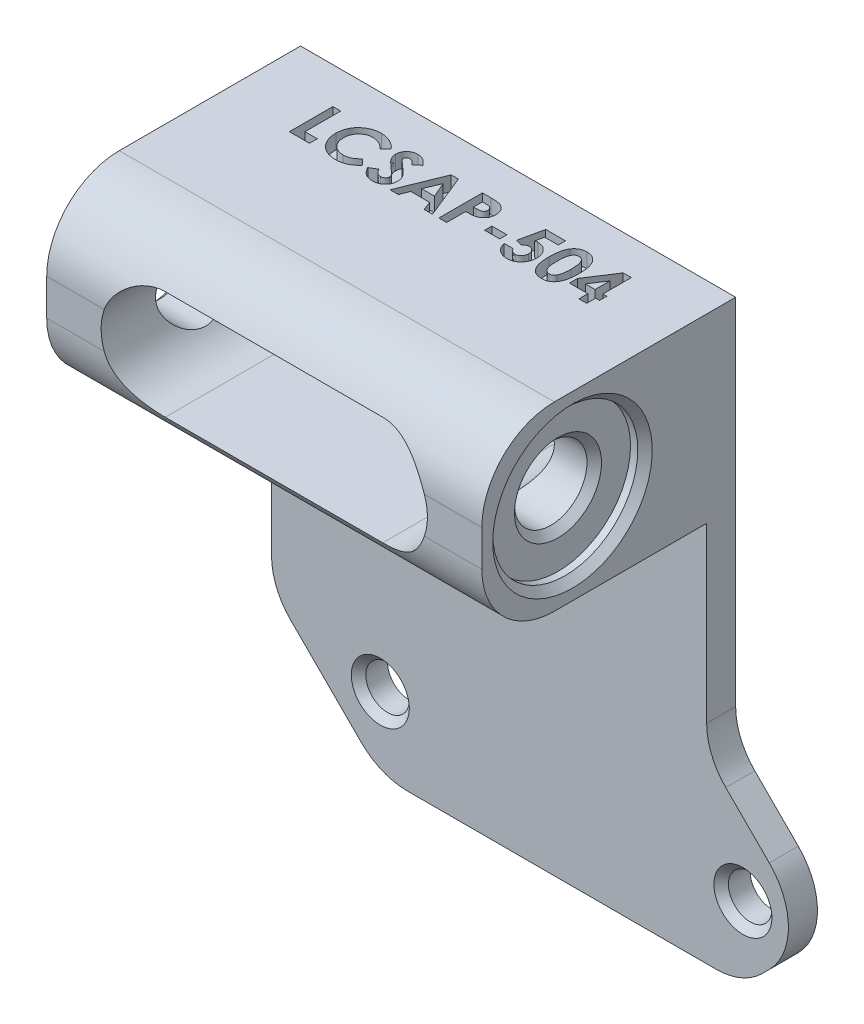
SolidWorks part; units mm, degrees
ref_plane "Front Plane" through (0, 0, 0) normal (0, 0, 1) x (1, 0, 0)
ref_plane "Top Plane" through (0, 0, 0) normal (0, 1, 0) x (1, 0, 0)
ref_plane "Right Plane" through (0, 0, 0) normal (1, 0, 0) x (0, 0, -1)
sketch "Sketch1" plane through (0, 0, 0) normal (0, 0, 1) x (1, 0, 0)
  line L0 (0, 0) -> (50.8, 0)
  line L1 (0, 0) -> (0, -15.875)
  line L3 (9.525, -49.276) -> (41.275, -49.276)
  line L5 (50.8, 0) -> (50.8, -15.875)
  line L7 (9.525, -42.926) -> (25.4, -49.276) construction
  line L8 (25.4, -49.276) -> (41.275, -42.926) construction
  line L9 (0, -15.875) -> (50.8, -15.875)
  line L10 (9.525, -49.276) -> (0, -39.751)
  line L11 (0, -39.751) -> (0, -15.875)
  line L12 (41.275, -49.276) -> (50.8, -39.751)
  line L13 (50.8, -39.751) -> (50.8, -15.875)
  circle A0 centre (9.525, -42.926) radius 1.905
  circle A1 centre (41.275, -42.926) radius 1.905
  dimension "D5" = 3.81
  dimension "D6" = 31.75
  dimension "D7" = 6.35
  dimension "D1" = 15.875
  dimension "D2" = 31.75
  dimension "D3" = 50.8
  dimension "D4" = 49.276
  dimension "D10" = 45
extrude "Boss-Extrude1" add sketch "Sketch1" along normal blind 2.54 contours L1 L9 L5 L0 | L9 L3 A1 A0 region at (25.4, -7.9375, 0) region at (25.4, -31.6514, 0)
extrude "Boss-Extrude2" add sketch "Sketch1<3>" along normal blind 22.225 contours L1 L9 L5 L0 region at (25.4, -7.9375, 0)
sketch "Sketch1<3>" plane through (0, 0, 0) normal (0, 0, 1) x (1, 0, 0) same geometry as "Sketch1"
sketch "Sketch7" plane through (0, 0, 22.225) normal (0, 0, 1) x (1, 0, 0)
  line L1 (50.8, 0) -> (38.1, 0)
  line L2 (50.8, 0) -> (50.8, -33.401)
  line L3 (50.8, -33.401) -> (38.1, -33.401) construction
  line L4 (38.1, 0) -> (38.1, -33.401)
  line L9 (38.1, -33.401) -> (50.8, -46.101)
  line L10 (50.8, -46.101) -> (50.8, -33.401)
  line L11 (44.45, -39.751) -> (41.275, -42.926) construction
  line L12 (41.275, -42.926) -> (44.45, -46.101) construction
  line L14 (41.275, -49.276) -> (50.8, -39.751) construction
  dimension "D1" = 12.7
  dimension "D2" = 45
extrude "Cut-Extrude6" cut sketch "Sketch7" against normal through all
fillet "Fillet2" radius 5.715 5 edges at (0, -39.751, 1.27) (9.525, -49.276, 1.27) (41.275, -49.276, 1.27) (38.1, -33.401, 1.27) (47.625, -42.926, 1.27)
sketch "Sketch2" plane through (38.1, 0, 0) normal (1, 0, 0) x (0, 0, -1)
  line L0 (-22.225, -15.875) -> (-6.35, 0) construction
  line L1 (0, 0) -> (-22.225, 0) construction
  line L2 (-22.225, 0) -> (-22.225, -15.875) construction
  circle A0 centre (-14.2875, -7.9375) radius 3.175
  dimension "D1" = 6.35
  dimension "D2" = 15.875
  dimension "D3" = 15.875
extrude "Cut-Extrude1" cut sketch "Sketch2" against normal through all
sketch "Sketch3" plane through (38.1, 0, 0) normal (1, 0, 0) x (0, 0, -1)
  circle A0 centre (-14.2875, -7.9375) radius 6.35
  dimension "D1" = 12.7
extrude "Cut-Extrude2" cut sketch "Sketch3" against normal blind 1.27
sketch "Sketch4" plane through (0, 0, 0) normal (-1, 0, 0) x (0, 0, 1)
  circle A0 centre (14.2875, -7.9375) radius 6.35
  circle A1 centre (14.2875, -7.9375) radius 3.175 construction
  dimension "D1" = 12.7
extrude "Cut-Extrude3" cut sketch "Sketch4" against normal blind 1.27
fillet "Fillet1" radius 6.35 2 edges at (19.05, -15.875, 22.225) (19.05, 0, 22.225)
chamfer "Chamfer1" distance 0.635 angle 45 6 edges at (1.27, -11.1125, 14.2875) (36.83, -7.9375, 11.1125) (0, -14.2875, 14.2875) (43.18, -42.926, 2.54) (11.43, -42.926, 2.54) (38.1, -7.9375, 7.9375)
sketch "Sketch5" plane through (0, 0, 22.225) normal (0, 0, 1) x (1, 0, 0)
  line L0 (9.525, -7.9375) -> (28.575, -7.9375) construction
  line L1 (9.525, -3.175) -> (28.575, -3.175)
  line L2 (9.525, -12.7) -> (28.575, -12.7)
  line L3 (0, -6.35) -> (0, -9.525) construction
  line L4 (19.05, -9.525) -> (19.05, -7.9375) construction
  line L5 (0, -9.525) -> (38.1, -9.525) construction
  arc A0 (9.525, -3.175) -> (9.525, -12.7) centre (9.525, -7.9375) ccw
  arc A1 (28.575, -12.7) -> (28.575, -3.175) centre (28.575, -7.9375) ccw
  point P2 (19.05, -7.9375)
  point P10 (0, -7.9375)
  dimension "D2" = 4.7625
  dimension "D1" = 19.05
extrude "Cut-Extrude4" cut sketch "Sketch5" against normal through all
sketch "Sketch6" plane through (0, 0, 0) normal (0, 1, 0) x (1, 0, 0)
  line L0 (38.1, -6.985) -> (0, -6.985) construction
  line L2 (0, -15.875) -> (0, 0) construction
  line L3 (0, 0) -> (38.1, 0) construction
  line L4 (38.1, 0) -> (38.1, -15.875) construction
  text T0 "<b>LCSAP-504</b>" font "Century Gothic" height 3.81
  dimension "D1" = 6.985
extrude "Cut-Extrude5" cut sketch "Sketch6" against normal blind 1.27
